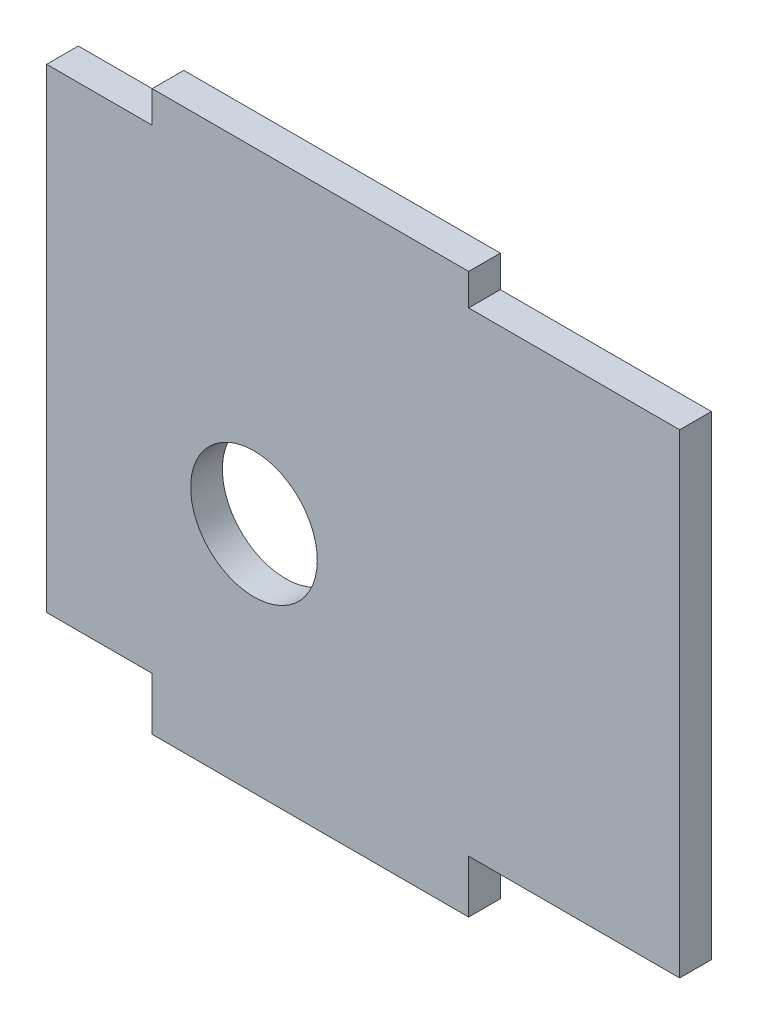
SolidWorks part; units mm, degrees
material "PVC rigido"
ref_plane "Piano frontale" through (0, 0, 0) normal (0, 0, 1) x (1, 0, 0)
ref_plane "Piano superiore" through (0, 0, 0) normal (0, 1, 0) x (1, 0, 0)
ref_plane "Piano destro" through (0, 0, 0) normal (1, 0, 0) x (0, 0, -1)
sketch "Schizzo1" plane through (0, 0, 0) normal (0, 0, 1) x (1, 0, 0)
  line L0 (47.5, -50) -> (17.5, -50) construction
  line L1 (17.5, 3) -> (47.5, 3)
  line L2 (17.5, 3) -> (17.5, -50)
  line L3 (17.5, -50) -> (47.5, -50)
  line L4 (47.5, 3) -> (47.5, -50)
  line L5 (47.5, 3) -> (17.5, 3) construction
extrude "Estrusione-Estrusione1" add sketch "Schizzo1" along normal blind 3
sketch "Schizzo3" plane through (0, 0, 3) normal (0, 0, 1) x (1, 0, 0)
  line L0 (17.5, 3) -> (17.5, -50) construction
  line L1 (17.5, 0) -> (7.5, 0)
  line L2 (17.5, 0) -> (17.5, -45)
  line L3 (17.5, -45) -> (7.5, -45)
  line L4 (7.5, 0) -> (7.5, -45)
  line L5 (47.5, -50) -> (47.5, 3) construction
  line L6 (47.5, 0) -> (67.5, 0)
  line L7 (47.5, 0) -> (47.5, -45)
  line L8 (47.5, -45) -> (67.5, -45)
  line L9 (67.5, 0) -> (67.5, -45)
  line L10 (8, -45) -> (17.5, -45) construction
  line L11 (47.5, 0) -> (57, 0) construction
  dimension "D1" = 10
  dimension "D2" = 20
extrude "Estrusione-Estrusione2" add sketch "Schizzo3" against normal up to surface (3 mm away) up to face at (32.5, -23.5, 0)
ref_plane "Piano1" through (65, -50, -140) normal (0, 1, 0) x (1, 0, 0)
sketch "Schizzo5" plane through (0, 0, 3) normal (0, 0, 1) x (1, 0, 0)
  circle A0 centre (27.15, -27.9) radius 6
  circle A1 centre (27.15, -27.9) radius 6 construction
extrude "Taglio-Estrusione1" cut sketch "Schizzo5" against normal through all
